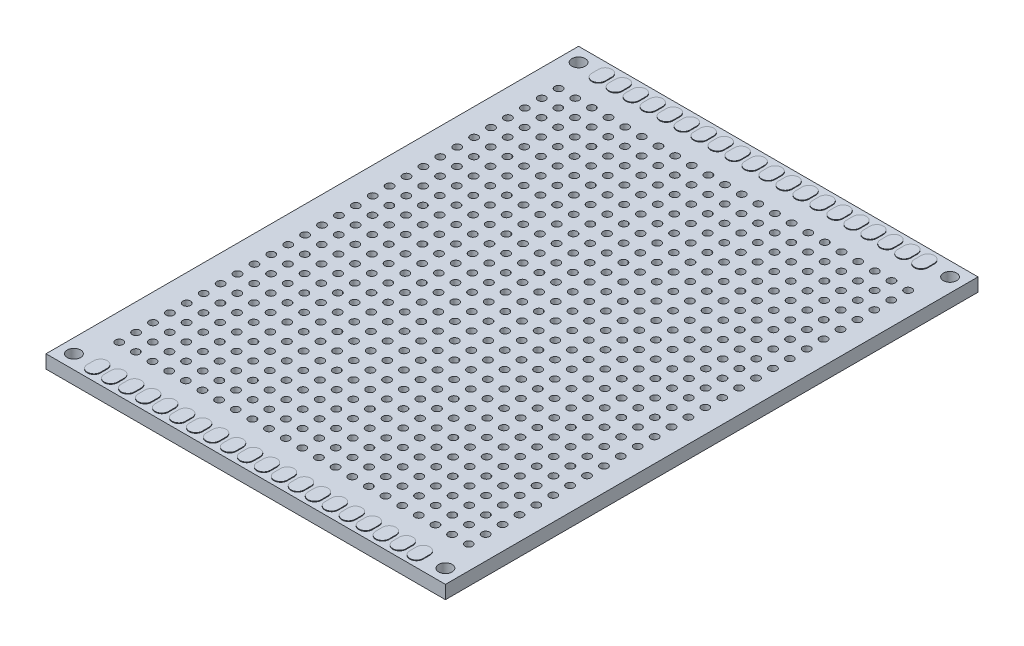
SolidWorks part; units mm, degrees
ref_plane "Front Plane" through (0, 0, 0) normal (0, 0, 1) x (1, 0, 0)
ref_plane "Top Plane" through (0, 0, 0) normal (0, 1, 0) x (1, 0, 0)
ref_plane "Right Plane" through (0, 0, 0) normal (1, 0, 0) x (0, 0, -1)
sketch "Sketch1" plane through (0, 0, 0) normal (0, 1, 0) x (1, 0, 0)
  line L0 (4, 73) -> (6.5, 73) construction
  line L1 (0, 80) -> (60, 80)
  line L2 (0, 80) -> (0, 0)
  line L3 (0, 0) -> (60, 0)
  line L4 (60, 80) -> (60, 0)
  circle A0 centre (2.1, 77.9) radius 1
  circle A1 centre (57.9, 77.9) radius 1
  circle A2 centre (2.1, 2.1) radius 1
  circle A3 centre (57.9, 2.1) radius 1
  circle A4 centre (4, 73) radius 0.575
  circle A5 centre (6.5, 73) radius 0.575
  circle A6 centre (9, 73) radius 0.575
  circle A7 centre (11.5, 73) radius 0.575
  circle A8 centre (14, 73) radius 0.575
  circle A9 centre (16.5, 73) radius 0.575
  circle A10 centre (19, 73) radius 0.575
  circle A11 centre (21.5, 73) radius 0.575
  circle A12 centre (24, 73) radius 0.575
  circle A13 centre (26.5, 73) radius 0.575
  circle A14 centre (29, 73) radius 0.575
  circle A15 centre (31.5, 73) radius 0.575
  circle A16 centre (34, 73) radius 0.575
  circle A17 centre (36.5, 73) radius 0.575
  circle A18 centre (39, 73) radius 0.575
  circle A19 centre (41.5, 73) radius 0.575
  circle A20 centre (44, 73) radius 0.575
  circle A21 centre (46.5, 73) radius 0.575
  circle A22 centre (49, 73) radius 0.575
  circle A23 centre (51.5, 73) radius 0.575
  circle A24 centre (54, 73) radius 0.575
  circle A25 centre (56.5, 73) radius 0.575
  circle A26 centre (6.5, 70.4615) radius 0.575
  circle A27 centre (9, 70.4615) radius 0.575
  circle A28 centre (11.5, 70.4615) radius 0.575
  circle A29 centre (14, 70.4615) radius 0.575
  circle A30 centre (16.5, 70.4615) radius 0.575
  circle A31 centre (19, 70.4615) radius 0.575
  circle A32 centre (21.5, 70.4615) radius 0.575
  circle A33 centre (24, 70.4615) radius 0.575
  circle A34 centre (26.5, 70.4615) radius 0.575
  circle A35 centre (29, 70.4615) radius 0.575
  circle A36 centre (31.5, 70.4615) radius 0.575
  circle A37 centre (34, 70.4615) radius 0.575
  circle A38 centre (36.5, 70.4615) radius 0.575
  circle A39 centre (39, 70.4615) radius 0.575
  circle A40 centre (41.5, 70.4615) radius 0.575
  circle A41 centre (44, 70.4615) radius 0.575
  circle A42 centre (46.5, 70.4615) radius 0.575
  circle A43 centre (49, 70.4615) radius 0.575
  circle A44 centre (51.5, 70.4615) radius 0.575
  circle A45 centre (54, 70.4615) radius 0.575
  circle A46 centre (56.5, 70.4615) radius 0.575
  circle A47 centre (6.5, 67.9231) radius 0.575
  circle A48 centre (9, 67.9231) radius 0.575
  circle A49 centre (11.5, 67.9231) radius 0.575
  circle A50 centre (14, 67.9231) radius 0.575
  circle A51 centre (16.5, 67.9231) radius 0.575
  circle A52 centre (19, 67.9231) radius 0.575
  circle A53 centre (21.5, 67.9231) radius 0.575
  circle A54 centre (24, 67.9231) radius 0.575
  circle A55 centre (26.5, 67.9231) radius 0.575
  circle A56 centre (29, 67.9231) radius 0.575
  circle A57 centre (31.5, 67.9231) radius 0.575
  circle A58 centre (34, 67.9231) radius 0.575
  circle A59 centre (36.5, 67.9231) radius 0.575
  circle A60 centre (39, 67.9231) radius 0.575
  circle A61 centre (41.5, 67.9231) radius 0.575
  circle A62 centre (44, 67.9231) radius 0.575
  circle A63 centre (46.5, 67.9231) radius 0.575
  circle A64 centre (49, 67.9231) radius 0.575
  circle A65 centre (51.5, 67.9231) radius 0.575
  circle A66 centre (54, 67.9231) radius 0.575
  circle A67 centre (56.5, 67.9231) radius 0.575
  circle A68 centre (6.5, 65.3846) radius 0.575
  circle A69 centre (9, 65.3846) radius 0.575
  circle A70 centre (11.5, 65.3846) radius 0.575
  circle A71 centre (14, 65.3846) radius 0.575
  circle A72 centre (16.5, 65.3846) radius 0.575
  circle A73 centre (19, 65.3846) radius 0.575
  circle A74 centre (21.5, 65.3846) radius 0.575
  circle A75 centre (24, 65.3846) radius 0.575
  circle A76 centre (26.5, 65.3846) radius 0.575
  circle A77 centre (29, 65.3846) radius 0.575
  circle A78 centre (31.5, 65.3846) radius 0.575
  circle A79 centre (34, 65.3846) radius 0.575
  circle A80 centre (36.5, 65.3846) radius 0.575
  circle A81 centre (39, 65.3846) radius 0.575
  circle A82 centre (41.5, 65.3846) radius 0.575
  circle A83 centre (44, 65.3846) radius 0.575
  circle A84 centre (46.5, 65.3846) radius 0.575
  circle A85 centre (49, 65.3846) radius 0.575
  circle A86 centre (51.5, 65.3846) radius 0.575
  circle A87 centre (54, 65.3846) radius 0.575
  circle A88 centre (56.5, 65.3846) radius 0.575
  circle A89 centre (6.5, 62.8462) radius 0.575
  circle A90 centre (9, 62.8462) radius 0.575
  circle A91 centre (11.5, 62.8462) radius 0.575
  circle A92 centre (14, 62.8462) radius 0.575
  circle A93 centre (16.5, 62.8462) radius 0.575
  circle A94 centre (19, 62.8462) radius 0.575
  circle A95 centre (21.5, 62.8462) radius 0.575
  circle A96 centre (24, 62.8462) radius 0.575
  circle A97 centre (26.5, 62.8462) radius 0.575
  circle A98 centre (29, 62.8462) radius 0.575
  circle A99 centre (31.5, 62.8462) radius 0.575
  circle A100 centre (34, 62.8462) radius 0.575
  circle A101 centre (36.5, 62.8462) radius 0.575
  circle A102 centre (39, 62.8462) radius 0.575
  circle A103 centre (41.5, 62.8462) radius 0.575
  circle A104 centre (44, 62.8462) radius 0.575
  circle A105 centre (46.5, 62.8462) radius 0.575
  circle A106 centre (49, 62.8462) radius 0.575
  circle A107 centre (51.5, 62.8462) radius 0.575
  circle A108 centre (54, 62.8462) radius 0.575
  circle A109 centre (56.5, 62.8462) radius 0.575
  circle A110 centre (6.5, 60.3077) radius 0.575
  circle A111 centre (9, 60.3077) radius 0.575
  circle A112 centre (11.5, 60.3077) radius 0.575
  circle A113 centre (14, 60.3077) radius 0.575
  circle A114 centre (16.5, 60.3077) radius 0.575
  circle A115 centre (19, 60.3077) radius 0.575
  circle A116 centre (21.5, 60.3077) radius 0.575
  circle A117 centre (24, 60.3077) radius 0.575
  circle A118 centre (26.5, 60.3077) radius 0.575
  circle A119 centre (29, 60.3077) radius 0.575
  circle A120 centre (31.5, 60.3077) radius 0.575
  circle A121 centre (34, 60.3077) radius 0.575
  circle A122 centre (36.5, 60.3077) radius 0.575
  circle A123 centre (39, 60.3077) radius 0.575
  circle A124 centre (41.5, 60.3077) radius 0.575
  circle A125 centre (44, 60.3077) radius 0.575
  circle A126 centre (46.5, 60.3077) radius 0.575
  circle A127 centre (49, 60.3077) radius 0.575
  circle A128 centre (51.5, 60.3077) radius 0.575
  circle A129 centre (54, 60.3077) radius 0.575
  circle A130 centre (56.5, 60.3077) radius 0.575
  circle A131 centre (6.5, 57.7692) radius 0.575
  circle A132 centre (9, 57.7692) radius 0.575
  circle A133 centre (11.5, 57.7692) radius 0.575
  circle A134 centre (14, 57.7692) radius 0.575
  circle A135 centre (16.5, 57.7692) radius 0.575
  circle A136 centre (19, 57.7692) radius 0.575
  circle A137 centre (21.5, 57.7692) radius 0.575
  circle A138 centre (24, 57.7692) radius 0.575
  circle A139 centre (26.5, 57.7692) radius 0.575
  circle A140 centre (29, 57.7692) radius 0.575
  circle A141 centre (31.5, 57.7692) radius 0.575
  circle A142 centre (34, 57.7692) radius 0.575
  circle A143 centre (36.5, 57.7692) radius 0.575
  circle A144 centre (39, 57.7692) radius 0.575
  circle A145 centre (41.5, 57.7692) radius 0.575
  circle A146 centre (44, 57.7692) radius 0.575
  circle A147 centre (46.5, 57.7692) radius 0.575
  circle A148 centre (49, 57.7692) radius 0.575
  circle A149 centre (51.5, 57.7692) radius 0.575
  circle A150 centre (54, 57.7692) radius 0.575
  circle A151 centre (56.5, 57.7692) radius 0.575
  circle A152 centre (6.5, 55.2308) radius 0.575
  circle A153 centre (9, 55.2308) radius 0.575
  circle A154 centre (11.5, 55.2308) radius 0.575
  circle A155 centre (14, 55.2308) radius 0.575
  circle A156 centre (16.5, 55.2308) radius 0.575
  circle A157 centre (19, 55.2308) radius 0.575
  circle A158 centre (21.5, 55.2308) radius 0.575
  circle A159 centre (24, 55.2308) radius 0.575
  circle A160 centre (26.5, 55.2308) radius 0.575
  circle A161 centre (29, 55.2308) radius 0.575
  circle A162 centre (31.5, 55.2308) radius 0.575
  circle A163 centre (34, 55.2308) radius 0.575
  circle A164 centre (36.5, 55.2308) radius 0.575
  circle A165 centre (39, 55.2308) radius 0.575
  circle A166 centre (41.5, 55.2308) radius 0.575
  circle A167 centre (44, 55.2308) radius 0.575
  circle A168 centre (46.5, 55.2308) radius 0.575
  circle A169 centre (49, 55.2308) radius 0.575
  circle A170 centre (51.5, 55.2308) radius 0.575
  circle A171 centre (54, 55.2308) radius 0.575
  circle A172 centre (56.5, 55.2308) radius 0.575
  circle A173 centre (6.5, 52.6923) radius 0.575
  circle A174 centre (9, 52.6923) radius 0.575
  circle A175 centre (11.5, 52.6923) radius 0.575
  circle A176 centre (14, 52.6923) radius 0.575
  circle A177 centre (16.5, 52.6923) radius 0.575
  circle A178 centre (19, 52.6923) radius 0.575
  circle A179 centre (21.5, 52.6923) radius 0.575
  circle A180 centre (24, 52.6923) radius 0.575
  circle A181 centre (26.5, 52.6923) radius 0.575
  circle A182 centre (29, 52.6923) radius 0.575
  circle A183 centre (31.5, 52.6923) radius 0.575
  circle A184 centre (34, 52.6923) radius 0.575
  circle A185 centre (36.5, 52.6923) radius 0.575
  circle A186 centre (39, 52.6923) radius 0.575
  circle A187 centre (41.5, 52.6923) radius 0.575
  circle A188 centre (44, 52.6923) radius 0.575
  circle A189 centre (46.5, 52.6923) radius 0.575
  circle A190 centre (49, 52.6923) radius 0.575
  circle A191 centre (51.5, 52.6923) radius 0.575
  circle A192 centre (54, 52.6923) radius 0.575
  circle A193 centre (56.5, 52.6923) radius 0.575
  circle A194 centre (6.5, 50.1538) radius 0.575
  circle A195 centre (9, 50.1538) radius 0.575
  circle A196 centre (11.5, 50.1538) radius 0.575
  circle A197 centre (14, 50.1538) radius 0.575
  circle A198 centre (16.5, 50.1538) radius 0.575
  circle A199 centre (19, 50.1538) radius 0.575
  circle A200 centre (21.5, 50.1538) radius 0.575
  circle A201 centre (24, 50.1538) radius 0.575
  circle A202 centre (26.5, 50.1538) radius 0.575
  circle A203 centre (29, 50.1538) radius 0.575
  circle A204 centre (31.5, 50.1538) radius 0.575
  circle A205 centre (34, 50.1538) radius 0.575
  circle A206 centre (36.5, 50.1538) radius 0.575
  circle A207 centre (39, 50.1538) radius 0.575
  circle A208 centre (41.5, 50.1538) radius 0.575
  circle A209 centre (44, 50.1538) radius 0.575
  circle A210 centre (46.5, 50.1538) radius 0.575
  circle A211 centre (49, 50.1538) radius 0.575
  circle A212 centre (51.5, 50.1538) radius 0.575
  circle A213 centre (54, 50.1538) radius 0.575
  circle A214 centre (56.5, 50.1538) radius 0.575
  circle A215 centre (6.5, 47.6154) radius 0.575
  circle A216 centre (9, 47.6154) radius 0.575
  circle A217 centre (11.5, 47.6154) radius 0.575
  circle A218 centre (14, 47.6154) radius 0.575
  circle A219 centre (16.5, 47.6154) radius 0.575
  circle A220 centre (19, 47.6154) radius 0.575
  circle A221 centre (21.5, 47.6154) radius 0.575
  circle A222 centre (24, 47.6154) radius 0.575
  circle A223 centre (26.5, 47.6154) radius 0.575
  circle A224 centre (29, 47.6154) radius 0.575
  circle A225 centre (31.5, 47.6154) radius 0.575
  circle A226 centre (34, 47.6154) radius 0.575
  circle A227 centre (36.5, 47.6154) radius 0.575
  circle A228 centre (39, 47.6154) radius 0.575
  circle A229 centre (41.5, 47.6154) radius 0.575
  circle A230 centre (44, 47.6154) radius 0.575
  circle A231 centre (46.5, 47.6154) radius 0.575
  circle A232 centre (49, 47.6154) radius 0.575
  circle A233 centre (51.5, 47.6154) radius 0.575
  circle A234 centre (54, 47.6154) radius 0.575
  circle A235 centre (56.5, 47.6154) radius 0.575
  circle A236 centre (6.5, 45.0769) radius 0.575
  circle A237 centre (9, 45.0769) radius 0.575
  circle A238 centre (11.5, 45.0769) radius 0.575
  circle A239 centre (14, 45.0769) radius 0.575
  circle A240 centre (16.5, 45.0769) radius 0.575
  circle A241 centre (19, 45.0769) radius 0.575
  circle A242 centre (21.5, 45.0769) radius 0.575
  circle A243 centre (24, 45.0769) radius 0.575
  circle A244 centre (26.5, 45.0769) radius 0.575
  circle A245 centre (29, 45.0769) radius 0.575
  circle A246 centre (31.5, 45.0769) radius 0.575
  circle A247 centre (34, 45.0769) radius 0.575
  circle A248 centre (36.5, 45.0769) radius 0.575
  circle A249 centre (39, 45.0769) radius 0.575
  circle A250 centre (41.5, 45.0769) radius 0.575
  circle A251 centre (44, 45.0769) radius 0.575
  circle A252 centre (46.5, 45.0769) radius 0.575
  circle A253 centre (49, 45.0769) radius 0.575
  circle A254 centre (51.5, 45.0769) radius 0.575
  circle A255 centre (54, 45.0769) radius 0.575
  circle A256 centre (56.5, 45.0769) radius 0.575
  circle A257 centre (6.5, 42.5385) radius 0.575
  circle A258 centre (9, 42.5385) radius 0.575
  circle A259 centre (11.5, 42.5385) radius 0.575
  circle A260 centre (14, 42.5385) radius 0.575
  circle A261 centre (16.5, 42.5385) radius 0.575
  circle A262 centre (19, 42.5385) radius 0.575
  circle A263 centre (21.5, 42.5385) radius 0.575
  circle A264 centre (24, 42.5385) radius 0.575
  circle A265 centre (26.5, 42.5385) radius 0.575
  circle A266 centre (29, 42.5385) radius 0.575
  circle A267 centre (31.5, 42.5385) radius 0.575
  circle A268 centre (34, 42.5385) radius 0.575
  circle A269 centre (36.5, 42.5385) radius 0.575
  circle A270 centre (39, 42.5385) radius 0.575
  circle A271 centre (41.5, 42.5385) radius 0.575
  circle A272 centre (44, 42.5385) radius 0.575
  circle A273 centre (46.5, 42.5385) radius 0.575
  circle A274 centre (49, 42.5385) radius 0.575
  circle A275 centre (51.5, 42.5385) radius 0.575
  circle A276 centre (54, 42.5385) radius 0.575
  circle A277 centre (56.5, 42.5385) radius 0.575
  circle A278 centre (6.5, 40) radius 0.575
  circle A279 centre (9, 40) radius 0.575
  circle A280 centre (11.5, 40) radius 0.575
  circle A281 centre (14, 40) radius 0.575
  circle A282 centre (16.5, 40) radius 0.575
  circle A283 centre (19, 40) radius 0.575
  circle A284 centre (21.5, 40) radius 0.575
  circle A285 centre (24, 40) radius 0.575
  circle A286 centre (26.5, 40) radius 0.575
  circle A287 centre (29, 40) radius 0.575
  circle A288 centre (31.5, 40) radius 0.575
  circle A289 centre (34, 40) radius 0.575
  circle A290 centre (36.5, 40) radius 0.575
  circle A291 centre (39, 40) radius 0.575
  circle A292 centre (41.5, 40) radius 0.575
  circle A293 centre (44, 40) radius 0.575
  circle A294 centre (46.5, 40) radius 0.575
  circle A295 centre (49, 40) radius 0.575
  circle A296 centre (51.5, 40) radius 0.575
  circle A297 centre (54, 40) radius 0.575
  circle A298 centre (56.5, 40) radius 0.575
  circle A299 centre (6.5, 37.4615) radius 0.575
  circle A300 centre (9, 37.4615) radius 0.575
  circle A301 centre (11.5, 37.4615) radius 0.575
  circle A302 centre (14, 37.4615) radius 0.575
  circle A303 centre (16.5, 37.4615) radius 0.575
  circle A304 centre (19, 37.4615) radius 0.575
  circle A305 centre (21.5, 37.4615) radius 0.575
  circle A306 centre (24, 37.4615) radius 0.575
  circle A307 centre (26.5, 37.4615) radius 0.575
  circle A308 centre (29, 37.4615) radius 0.575
  circle A309 centre (31.5, 37.4615) radius 0.575
  circle A310 centre (34, 37.4615) radius 0.575
  circle A311 centre (36.5, 37.4615) radius 0.575
  circle A312 centre (39, 37.4615) radius 0.575
  circle A313 centre (41.5, 37.4615) radius 0.575
  circle A314 centre (44, 37.4615) radius 0.575
  circle A315 centre (46.5, 37.4615) radius 0.575
  circle A316 centre (49, 37.4615) radius 0.575
  circle A317 centre (51.5, 37.4615) radius 0.575
  circle A318 centre (54, 37.4615) radius 0.575
  circle A319 centre (56.5, 37.4615) radius 0.575
  circle A320 centre (6.5, 34.9231) radius 0.575
  circle A321 centre (9, 34.9231) radius 0.575
  circle A322 centre (11.5, 34.9231) radius 0.575
  circle A323 centre (14, 34.9231) radius 0.575
  circle A324 centre (16.5, 34.9231) radius 0.575
  circle A325 centre (19, 34.9231) radius 0.575
  circle A326 centre (21.5, 34.9231) radius 0.575
  circle A327 centre (24, 34.9231) radius 0.575
  circle A328 centre (26.5, 34.9231) radius 0.575
  circle A329 centre (29, 34.9231) radius 0.575
  circle A330 centre (31.5, 34.9231) radius 0.575
  circle A331 centre (34, 34.9231) radius 0.575
  circle A332 centre (36.5, 34.9231) radius 0.575
  circle A333 centre (39, 34.9231) radius 0.575
  circle A334 centre (41.5, 34.9231) radius 0.575
  circle A335 centre (44, 34.9231) radius 0.575
  circle A336 centre (46.5, 34.9231) radius 0.575
  circle A337 centre (49, 34.9231) radius 0.575
  circle A338 centre (51.5, 34.9231) radius 0.575
  circle A339 centre (54, 34.9231) radius 0.575
  circle A340 centre (56.5, 34.9231) radius 0.575
  circle A341 centre (6.5, 32.3846) radius 0.575
  circle A342 centre (9, 32.3846) radius 0.575
  circle A343 centre (11.5, 32.3846) radius 0.575
  circle A344 centre (14, 32.3846) radius 0.575
  circle A345 centre (16.5, 32.3846) radius 0.575
  circle A346 centre (19, 32.3846) radius 0.575
  circle A347 centre (21.5, 32.3846) radius 0.575
  circle A348 centre (24, 32.3846) radius 0.575
  circle A349 centre (26.5, 32.3846) radius 0.575
  circle A350 centre (29, 32.3846) radius 0.575
  circle A351 centre (31.5, 32.3846) radius 0.575
  circle A352 centre (34, 32.3846) radius 0.575
  circle A353 centre (36.5, 32.3846) radius 0.575
  circle A354 centre (39, 32.3846) radius 0.575
  circle A355 centre (41.5, 32.3846) radius 0.575
  circle A356 centre (44, 32.3846) radius 0.575
  circle A357 centre (46.5, 32.3846) radius 0.575
  circle A358 centre (49, 32.3846) radius 0.575
  circle A359 centre (51.5, 32.3846) radius 0.575
  circle A360 centre (54, 32.3846) radius 0.575
  circle A361 centre (56.5, 32.3846) radius 0.575
  circle A362 centre (6.5, 29.8462) radius 0.575
  circle A363 centre (9, 29.8462) radius 0.575
  circle A364 centre (11.5, 29.8462) radius 0.575
  circle A365 centre (14, 29.8462) radius 0.575
  circle A366 centre (16.5, 29.8462) radius 0.575
  circle A367 centre (19, 29.8462) radius 0.575
  circle A368 centre (21.5, 29.8462) radius 0.575
  circle A369 centre (24, 29.8462) radius 0.575
  circle A370 centre (26.5, 29.8462) radius 0.575
  circle A371 centre (29, 29.8462) radius 0.575
  circle A372 centre (31.5, 29.8462) radius 0.575
  circle A373 centre (34, 29.8462) radius 0.575
  circle A374 centre (36.5, 29.8462) radius 0.575
  circle A375 centre (39, 29.8462) radius 0.575
  circle A376 centre (41.5, 29.8462) radius 0.575
  circle A377 centre (44, 29.8462) radius 0.575
  circle A378 centre (46.5, 29.8462) radius 0.575
  circle A379 centre (49, 29.8462) radius 0.575
  circle A380 centre (51.5, 29.8462) radius 0.575
  circle A381 centre (54, 29.8462) radius 0.575
  circle A382 centre (56.5, 29.8462) radius 0.575
  circle A383 centre (6.5, 27.3077) radius 0.575
  circle A384 centre (9, 27.3077) radius 0.575
  circle A385 centre (11.5, 27.3077) radius 0.575
  circle A386 centre (14, 27.3077) radius 0.575
  circle A387 centre (16.5, 27.3077) radius 0.575
  circle A388 centre (19, 27.3077) radius 0.575
  circle A389 centre (21.5, 27.3077) radius 0.575
  circle A390 centre (24, 27.3077) radius 0.575
  circle A391 centre (26.5, 27.3077) radius 0.575
  circle A392 centre (29, 27.3077) radius 0.575
  circle A393 centre (31.5, 27.3077) radius 0.575
  circle A394 centre (34, 27.3077) radius 0.575
  circle A395 centre (36.5, 27.3077) radius 0.575
  circle A396 centre (39, 27.3077) radius 0.575
  circle A397 centre (41.5, 27.3077) radius 0.575
  circle A398 centre (44, 27.3077) radius 0.575
  circle A399 centre (46.5, 27.3077) radius 0.575
  circle A400 centre (49, 27.3077) radius 0.575
  circle A401 centre (51.5, 27.3077) radius 0.575
  circle A402 centre (54, 27.3077) radius 0.575
  circle A403 centre (56.5, 27.3077) radius 0.575
  circle A404 centre (6.5, 24.7692) radius 0.575
  circle A405 centre (9, 24.7692) radius 0.575
  circle A406 centre (11.5, 24.7692) radius 0.575
  circle A407 centre (14, 24.7692) radius 0.575
  circle A408 centre (16.5, 24.7692) radius 0.575
  circle A409 centre (19, 24.7692) radius 0.575
  circle A410 centre (21.5, 24.7692) radius 0.575
  circle A411 centre (24, 24.7692) radius 0.575
  circle A412 centre (26.5, 24.7692) radius 0.575
  circle A413 centre (29, 24.7692) radius 0.575
  circle A414 centre (31.5, 24.7692) radius 0.575
  circle A415 centre (34, 24.7692) radius 0.575
  circle A416 centre (36.5, 24.7692) radius 0.575
  circle A417 centre (39, 24.7692) radius 0.575
  circle A418 centre (41.5, 24.7692) radius 0.575
  circle A419 centre (44, 24.7692) radius 0.575
  circle A420 centre (46.5, 24.7692) radius 0.575
  circle A421 centre (49, 24.7692) radius 0.575
  circle A422 centre (51.5, 24.7692) radius 0.575
  circle A423 centre (54, 24.7692) radius 0.575
  circle A424 centre (56.5, 24.7692) radius 0.575
  circle A425 centre (6.5, 22.2308) radius 0.575
  circle A426 centre (9, 22.2308) radius 0.575
  circle A427 centre (11.5, 22.2308) radius 0.575
  circle A428 centre (14, 22.2308) radius 0.575
  circle A429 centre (16.5, 22.2308) radius 0.575
  circle A430 centre (19, 22.2308) radius 0.575
  circle A431 centre (21.5, 22.2308) radius 0.575
  circle A432 centre (24, 22.2308) radius 0.575
  circle A433 centre (26.5, 22.2308) radius 0.575
  circle A434 centre (29, 22.2308) radius 0.575
  circle A435 centre (31.5, 22.2308) radius 0.575
  circle A436 centre (34, 22.2308) radius 0.575
  circle A437 centre (36.5, 22.2308) radius 0.575
  circle A438 centre (39, 22.2308) radius 0.575
  circle A439 centre (41.5, 22.2308) radius 0.575
  circle A440 centre (44, 22.2308) radius 0.575
  circle A441 centre (46.5, 22.2308) radius 0.575
  circle A442 centre (49, 22.2308) radius 0.575
  circle A443 centre (51.5, 22.2308) radius 0.575
  circle A444 centre (54, 22.2308) radius 0.575
  circle A445 centre (56.5, 22.2308) radius 0.575
  circle A446 centre (6.5, 19.6923) radius 0.575
  circle A447 centre (9, 19.6923) radius 0.575
  circle A448 centre (11.5, 19.6923) radius 0.575
  circle A449 centre (14, 19.6923) radius 0.575
  circle A450 centre (16.5, 19.6923) radius 0.575
  circle A451 centre (19, 19.6923) radius 0.575
  circle A452 centre (21.5, 19.6923) radius 0.575
  circle A453 centre (24, 19.6923) radius 0.575
  circle A454 centre (26.5, 19.6923) radius 0.575
  circle A455 centre (29, 19.6923) radius 0.575
  circle A456 centre (31.5, 19.6923) radius 0.575
  circle A457 centre (34, 19.6923) radius 0.575
  circle A458 centre (36.5, 19.6923) radius 0.575
  circle A459 centre (39, 19.6923) radius 0.575
  circle A460 centre (41.5, 19.6923) radius 0.575
  circle A461 centre (44, 19.6923) radius 0.575
  circle A462 centre (46.5, 19.6923) radius 0.575
  circle A463 centre (49, 19.6923) radius 0.575
  circle A464 centre (51.5, 19.6923) radius 0.575
  circle A465 centre (54, 19.6923) radius 0.575
  circle A466 centre (56.5, 19.6923) radius 0.575
  circle A467 centre (6.5, 17.1538) radius 0.575
  circle A468 centre (9, 17.1538) radius 0.575
  circle A469 centre (11.5, 17.1538) radius 0.575
  circle A470 centre (14, 17.1538) radius 0.575
  circle A471 centre (16.5, 17.1538) radius 0.575
  circle A472 centre (19, 17.1538) radius 0.575
  circle A473 centre (21.5, 17.1538) radius 0.575
  circle A474 centre (24, 17.1538) radius 0.575
  circle A475 centre (26.5, 17.1538) radius 0.575
  circle A476 centre (29, 17.1538) radius 0.575
  circle A477 centre (31.5, 17.1538) radius 0.575
  circle A478 centre (34, 17.1538) radius 0.575
  circle A479 centre (36.5, 17.1538) radius 0.575
  circle A480 centre (39, 17.1538) radius 0.575
  circle A481 centre (41.5, 17.1538) radius 0.575
  circle A482 centre (44, 17.1538) radius 0.575
  circle A483 centre (46.5, 17.1538) radius 0.575
  circle A484 centre (49, 17.1538) radius 0.575
  circle A485 centre (51.5, 17.1538) radius 0.575
  circle A486 centre (54, 17.1538) radius 0.575
  circle A487 centre (56.5, 17.1538) radius 0.575
  circle A488 centre (6.5, 14.6154) radius 0.575
  circle A489 centre (9, 14.6154) radius 0.575
  circle A490 centre (11.5, 14.6154) radius 0.575
  circle A491 centre (14, 14.6154) radius 0.575
  circle A492 centre (16.5, 14.6154) radius 0.575
  circle A493 centre (19, 14.6154) radius 0.575
  circle A494 centre (21.5, 14.6154) radius 0.575
  circle A495 centre (24, 14.6154) radius 0.575
  circle A496 centre (26.5, 14.6154) radius 0.575
  circle A497 centre (29, 14.6154) radius 0.575
  circle A498 centre (31.5, 14.6154) radius 0.575
  circle A499 centre (34, 14.6154) radius 0.575
  circle A500 centre (36.5, 14.6154) radius 0.575
  circle A501 centre (39, 14.6154) radius 0.575
  circle A502 centre (41.5, 14.6154) radius 0.575
  circle A503 centre (44, 14.6154) radius 0.575
  circle A504 centre (46.5, 14.6154) radius 0.575
  circle A505 centre (49, 14.6154) radius 0.575
  circle A506 centre (51.5, 14.6154) radius 0.575
  circle A507 centre (54, 14.6154) radius 0.575
  circle A508 centre (56.5, 14.6154) radius 0.575
  circle A509 centre (6.5, 12.0769) radius 0.575
  circle A510 centre (9, 12.0769) radius 0.575
  circle A511 centre (11.5, 12.0769) radius 0.575
  circle A512 centre (14, 12.0769) radius 0.575
  circle A513 centre (16.5, 12.0769) radius 0.575
  circle A514 centre (19, 12.0769) radius 0.575
  circle A515 centre (21.5, 12.0769) radius 0.575
  circle A516 centre (24, 12.0769) radius 0.575
  circle A517 centre (26.5, 12.0769) radius 0.575
  circle A518 centre (29, 12.0769) radius 0.575
  circle A519 centre (31.5, 12.0769) radius 0.575
  circle A520 centre (34, 12.0769) radius 0.575
  circle A521 centre (36.5, 12.0769) radius 0.575
  circle A522 centre (39, 12.0769) radius 0.575
  circle A523 centre (41.5, 12.0769) radius 0.575
  circle A524 centre (44, 12.0769) radius 0.575
  circle A525 centre (46.5, 12.0769) radius 0.575
  circle A526 centre (49, 12.0769) radius 0.575
  circle A527 centre (51.5, 12.0769) radius 0.575
  circle A528 centre (54, 12.0769) radius 0.575
  circle A529 centre (56.5, 12.0769) radius 0.575
  circle A530 centre (6.5, 9.5385) radius 0.575
  circle A531 centre (9, 9.5385) radius 0.575
  circle A532 centre (11.5, 9.5385) radius 0.575
  circle A533 centre (14, 9.5385) radius 0.575
  circle A534 centre (16.5, 9.5385) radius 0.575
  circle A535 centre (19, 9.5385) radius 0.575
  circle A536 centre (21.5, 9.5385) radius 0.575
  circle A537 centre (24, 9.5385) radius 0.575
  circle A538 centre (26.5, 9.5385) radius 0.575
  circle A539 centre (29, 9.5385) radius 0.575
  circle A540 centre (31.5, 9.5385) radius 0.575
  circle A541 centre (34, 9.5385) radius 0.575
  circle A542 centre (36.5, 9.5385) radius 0.575
  circle A543 centre (39, 9.5385) radius 0.575
  circle A544 centre (41.5, 9.5385) radius 0.575
  circle A545 centre (44, 9.5385) radius 0.575
  circle A546 centre (46.5, 9.5385) radius 0.575
  circle A547 centre (49, 9.5385) radius 0.575
  circle A548 centre (51.5, 9.5385) radius 0.575
  circle A549 centre (54, 9.5385) radius 0.575
  circle A550 centre (56.5, 9.5385) radius 0.575
  circle A551 centre (6.5, 7) radius 0.575
  circle A552 centre (9, 7) radius 0.575
  circle A553 centre (11.5, 7) radius 0.575
  circle A554 centre (14, 7) radius 0.575
  circle A555 centre (16.5, 7) radius 0.575
  circle A556 centre (19, 7) radius 0.575
  circle A557 centre (21.5, 7) radius 0.575
  circle A558 centre (24, 7) radius 0.575
  circle A559 centre (26.5, 7) radius 0.575
  circle A560 centre (29, 7) radius 0.575
  circle A561 centre (31.5, 7) radius 0.575
  circle A562 centre (34, 7) radius 0.575
  circle A563 centre (36.5, 7) radius 0.575
  circle A564 centre (39, 7) radius 0.575
  circle A565 centre (41.5, 7) radius 0.575
  circle A566 centre (44, 7) radius 0.575
  circle A567 centre (46.5, 7) radius 0.575
  circle A568 centre (49, 7) radius 0.575
  circle A569 centre (51.5, 7) radius 0.575
  circle A570 centre (54, 7) radius 0.575
  circle A571 centre (56.5, 7) radius 0.575
  circle A572 centre (4, 70.4615) radius 0.575
  circle A573 centre (4, 67.9231) radius 0.575
  circle A574 centre (4, 65.3846) radius 0.575
  circle A575 centre (4, 62.8462) radius 0.575
  circle A576 centre (4, 60.3077) radius 0.575
  circle A577 centre (4, 57.7692) radius 0.575
  circle A578 centre (4, 55.2308) radius 0.575
  circle A579 centre (4, 52.6923) radius 0.575
  circle A580 centre (4, 50.1538) radius 0.575
  circle A581 centre (4, 47.6154) radius 0.575
  circle A582 centre (4, 45.0769) radius 0.575
  circle A583 centre (4, 42.5385) radius 0.575
  circle A584 centre (4, 40) radius 0.575
  circle A585 centre (4, 37.4615) radius 0.575
  circle A586 centre (4, 34.9231) radius 0.575
  circle A587 centre (4, 32.3846) radius 0.575
  circle A588 centre (4, 29.8462) radius 0.575
  circle A589 centre (4, 27.3077) radius 0.575
  circle A590 centre (4, 24.7692) radius 0.575
  circle A591 centre (4, 22.2308) radius 0.575
  circle A592 centre (4, 19.6923) radius 0.575
  circle A593 centre (4, 17.1538) radius 0.575
  circle A594 centre (4, 14.6154) radius 0.575
  circle A595 centre (4, 12.0769) radius 0.575
  circle A596 centre (4, 9.5385) radius 0.575
  circle A597 centre (4, 7) radius 0.575
  dimension "D3" = 2
  dimension "D12" = 1.15
  dimension "D1" = 60
  dimension "D2" = 80
  dimension "D4" = 2.1
  dimension "D5" = 2.1
  dimension "D6" = 2.1
  dimension "D7" = 2.1
  dimension "D8" = 2.1
  dimension "D9" = 2.1
  dimension "D10" = 2.1
  dimension "D11" = 2.1
  dimension "D15" = 2.5
  dimension "D16" = 7
  dimension "D17" = 4
  dimension "D18" = 66
  dimension "D13" = 22
  dimension "D14" = 27
extrude "Boss-Extrude1" add sketch "Sketch1" along normal blind 2
sketch "Sketch2" plane through (0, 2, 0) normal (0, 1, 0) x (1, 0, 0)
  line L0 (5.6, 78.4) -> (5.6, 77.4) construction
  line L1 (6.6, 78.4) -> (6.6, 77.4)
  line L2 (4.6, 78.4) -> (4.6, 77.4)
  line L3 (4.3933, 79.4) -> (8.7363, 79.4) construction
  line L4 (4.162, 76.4) -> (8.5436, 76.4) construction
  line L5 (2.1, 77.9) -> (8.081, 77.9) construction
  line L6 (8.15, 78.4) -> (8.15, 77.4) construction
  line L7 (9.15, 78.4) -> (9.15, 77.4)
  line L8 (7.15, 78.4) -> (7.15, 77.4)
  line L9 (10.7, 78.4) -> (10.7, 77.4) construction
  line L10 (11.7, 78.4) -> (11.7, 77.4)
  line L11 (9.7, 78.4) -> (9.7, 77.4)
  line L12 (13.25, 78.4) -> (13.25, 77.4) construction
  line L13 (14.25, 78.4) -> (14.25, 77.4)
  line L14 (12.25, 78.4) -> (12.25, 77.4)
  line L15 (15.8, 78.4) -> (15.8, 77.4) construction
  line L16 (16.8, 78.4) -> (16.8, 77.4)
  line L17 (14.8, 78.4) -> (14.8, 77.4)
  line L18 (18.35, 78.4) -> (18.35, 77.4) construction
  line L19 (19.35, 78.4) -> (19.35, 77.4)
  line L20 (17.35, 78.4) -> (17.35, 77.4)
  line L21 (20.9, 78.4) -> (20.9, 77.4) construction
  line L22 (21.9, 78.4) -> (21.9, 77.4)
  line L23 (19.9, 78.4) -> (19.9, 77.4)
  line L24 (23.45, 78.4) -> (23.45, 77.4) construction
  line L25 (24.45, 78.4) -> (24.45, 77.4)
  line L26 (22.45, 78.4) -> (22.45, 77.4)
  line L27 (26, 78.4) -> (26, 77.4) construction
  line L28 (27, 78.4) -> (27, 77.4)
  line L29 (25, 78.4) -> (25, 77.4)
  line L30 (28.55, 78.4) -> (28.55, 77.4) construction
  line L31 (29.55, 78.4) -> (29.55, 77.4)
  line L32 (27.55, 78.4) -> (27.55, 77.4)
  line L33 (31.1, 78.4) -> (31.1, 77.4) construction
  line L34 (32.1, 78.4) -> (32.1, 77.4)
  line L35 (30.1, 78.4) -> (30.1, 77.4)
  line L36 (33.65, 78.4) -> (33.65, 77.4) construction
  line L37 (34.65, 78.4) -> (34.65, 77.4)
  line L38 (32.65, 78.4) -> (32.65, 77.4)
  line L39 (36.2, 78.4) -> (36.2, 77.4) construction
  line L40 (37.2, 78.4) -> (37.2, 77.4)
  line L41 (35.2, 78.4) -> (35.2, 77.4)
  line L42 (38.75, 78.4) -> (38.75, 77.4) construction
  line L43 (39.75, 78.4) -> (39.75, 77.4)
  line L44 (37.75, 78.4) -> (37.75, 77.4)
  line L45 (41.3, 78.4) -> (41.3, 77.4) construction
  line L46 (42.3, 78.4) -> (42.3, 77.4)
  line L47 (40.3, 78.4) -> (40.3, 77.4)
  line L48 (43.85, 78.4) -> (43.85, 77.4) construction
  line L49 (44.85, 78.4) -> (44.85, 77.4)
  line L50 (42.85, 78.4) -> (42.85, 77.4)
  line L51 (46.4, 78.4) -> (46.4, 77.4) construction
  line L52 (47.4, 78.4) -> (47.4, 77.4)
  line L53 (45.4, 78.4) -> (45.4, 77.4)
  line L54 (48.95, 78.4) -> (48.95, 77.4) construction
  line L55 (49.95, 78.4) -> (49.95, 77.4)
  line L56 (47.95, 78.4) -> (47.95, 77.4)
  line L57 (51.5, 78.4) -> (51.5, 77.4) construction
  line L58 (52.5, 78.4) -> (52.5, 77.4)
  line L59 (50.5, 78.4) -> (50.5, 77.4)
  line L60 (54.05, 78.4) -> (54.05, 77.4) construction
  line L61 (55.05, 78.4) -> (55.05, 77.4)
  line L62 (53.05, 78.4) -> (53.05, 77.4)
  line L63 (5.6, 78.4) -> (8.15, 78.4) construction
  line L64 (0, 40) -> (76.5553, 40) construction
  line L65 (0, 80) -> (0, 0) construction
  line L66 (5.6, 1.6) -> (5.6, 2.6) construction
  line L67 (6.6, 1.6) -> (6.6, 2.6)
  line L68 (4.6, 1.6) -> (4.6, 2.6)
  line L69 (8.15, 1.6) -> (8.15, 2.6) construction
  line L70 (9.15, 1.6) -> (9.15, 2.6)
  line L71 (7.15, 1.6) -> (7.15, 2.6)
  line L72 (10.7, 1.6) -> (10.7, 2.6) construction
  line L73 (11.7, 1.6) -> (11.7, 2.6)
  line L74 (9.7, 1.6) -> (9.7, 2.6)
  line L75 (13.25, 1.6) -> (13.25, 2.6) construction
  line L76 (14.25, 1.6) -> (14.25, 2.6)
  line L77 (12.25, 1.6) -> (12.25, 2.6)
  line L78 (15.8, 1.6) -> (15.8, 2.6) construction
  line L79 (16.8, 1.6) -> (16.8, 2.6)
  line L80 (14.8, 1.6) -> (14.8, 2.6)
  line L81 (18.35, 1.6) -> (18.35, 2.6) construction
  line L82 (19.35, 1.6) -> (19.35, 2.6)
  line L83 (17.35, 1.6) -> (17.35, 2.6)
  line L84 (20.9, 1.6) -> (20.9, 2.6) construction
  line L85 (21.9, 1.6) -> (21.9, 2.6)
  line L86 (19.9, 1.6) -> (19.9, 2.6)
  line L87 (23.45, 1.6) -> (23.45, 2.6) construction
  line L88 (24.45, 1.6) -> (24.45, 2.6)
  line L89 (22.45, 1.6) -> (22.45, 2.6)
  line L90 (26, 1.6) -> (26, 2.6) construction
  line L91 (27, 1.6) -> (27, 2.6)
  line L92 (25, 1.6) -> (25, 2.6)
  line L93 (28.55, 1.6) -> (28.55, 2.6) construction
  line L94 (29.55, 1.6) -> (29.55, 2.6)
  line L95 (27.55, 1.6) -> (27.55, 2.6)
  line L96 (31.1, 1.6) -> (31.1, 2.6) construction
  line L97 (32.1, 1.6) -> (32.1, 2.6)
  line L98 (30.1, 1.6) -> (30.1, 2.6)
  line L99 (33.65, 1.6) -> (33.65, 2.6) construction
  line L100 (34.65, 1.6) -> (34.65, 2.6)
  line L101 (32.65, 1.6) -> (32.65, 2.6)
  line L102 (36.2, 1.6) -> (36.2, 2.6) construction
  line L103 (37.2, 1.6) -> (37.2, 2.6)
  line L104 (35.2, 1.6) -> (35.2, 2.6)
  line L105 (38.75, 1.6) -> (38.75, 2.6) construction
  line L106 (39.75, 1.6) -> (39.75, 2.6)
  line L107 (37.75, 1.6) -> (37.75, 2.6)
  line L108 (41.3, 1.6) -> (41.3, 2.6) construction
  line L109 (42.3, 1.6) -> (42.3, 2.6)
  line L110 (40.3, 1.6) -> (40.3, 2.6)
  line L111 (43.85, 1.6) -> (43.85, 2.6) construction
  line L112 (44.85, 1.6) -> (44.85, 2.6)
  line L113 (42.85, 1.6) -> (42.85, 2.6)
  line L114 (46.4, 1.6) -> (46.4, 2.6) construction
  line L115 (47.4, 1.6) -> (47.4, 2.6)
  line L116 (45.4, 1.6) -> (45.4, 2.6)
  line L117 (48.95, 1.6) -> (48.95, 2.6) construction
  line L118 (49.95, 1.6) -> (49.95, 2.6)
  line L119 (47.95, 1.6) -> (47.95, 2.6)
  line L120 (51.5, 1.6) -> (51.5, 2.6) construction
  line L121 (52.5, 1.6) -> (52.5, 2.6)
  line L122 (50.5, 1.6) -> (50.5, 2.6)
  line L123 (54.05, 1.6) -> (54.05, 2.6) construction
  line L124 (55.05, 1.6) -> (55.05, 2.6)
  line L125 (53.05, 1.6) -> (53.05, 2.6)
  arc A0 (6.6, 78.4) -> (4.6, 78.4) centre (5.6, 78.4) ccw
  arc A1 (4.6, 77.4) -> (6.6, 77.4) centre (5.6, 77.4) ccw
  arc A2 (9.15, 78.4) -> (7.15, 78.4) centre (8.15, 78.4) ccw
  arc A3 (7.15, 77.4) -> (9.15, 77.4) centre (8.15, 77.4) ccw
  arc A4 (11.7, 78.4) -> (9.7, 78.4) centre (10.7, 78.4) ccw
  arc A5 (9.7, 77.4) -> (11.7, 77.4) centre (10.7, 77.4) ccw
  arc A6 (14.25, 78.4) -> (12.25, 78.4) centre (13.25, 78.4) ccw
  arc A7 (12.25, 77.4) -> (14.25, 77.4) centre (13.25, 77.4) ccw
  arc A8 (16.8, 78.4) -> (14.8, 78.4) centre (15.8, 78.4) ccw
  arc A9 (14.8, 77.4) -> (16.8, 77.4) centre (15.8, 77.4) ccw
  arc A10 (19.35, 78.4) -> (17.35, 78.4) centre (18.35, 78.4) ccw
  arc A11 (17.35, 77.4) -> (19.35, 77.4) centre (18.35, 77.4) ccw
  arc A12 (21.9, 78.4) -> (19.9, 78.4) centre (20.9, 78.4) ccw
  arc A13 (19.9, 77.4) -> (21.9, 77.4) centre (20.9, 77.4) ccw
  arc A14 (24.45, 78.4) -> (22.45, 78.4) centre (23.45, 78.4) ccw
  arc A15 (22.45, 77.4) -> (24.45, 77.4) centre (23.45, 77.4) ccw
  arc A16 (27, 78.4) -> (25, 78.4) centre (26, 78.4) ccw
  arc A17 (25, 77.4) -> (27, 77.4) centre (26, 77.4) ccw
  arc A18 (29.55, 78.4) -> (27.55, 78.4) centre (28.55, 78.4) ccw
  arc A19 (27.55, 77.4) -> (29.55, 77.4) centre (28.55, 77.4) ccw
  arc A20 (32.1, 78.4) -> (30.1, 78.4) centre (31.1, 78.4) ccw
  arc A21 (30.1, 77.4) -> (32.1, 77.4) centre (31.1, 77.4) ccw
  arc A22 (34.65, 78.4) -> (32.65, 78.4) centre (33.65, 78.4) ccw
  arc A23 (32.65, 77.4) -> (34.65, 77.4) centre (33.65, 77.4) ccw
  arc A24 (37.2, 78.4) -> (35.2, 78.4) centre (36.2, 78.4) ccw
  arc A25 (35.2, 77.4) -> (37.2, 77.4) centre (36.2, 77.4) ccw
  arc A26 (39.75, 78.4) -> (37.75, 78.4) centre (38.75, 78.4) ccw
  arc A27 (37.75, 77.4) -> (39.75, 77.4) centre (38.75, 77.4) ccw
  arc A28 (42.3, 78.4) -> (40.3, 78.4) centre (41.3, 78.4) ccw
  arc A29 (40.3, 77.4) -> (42.3, 77.4) centre (41.3, 77.4) ccw
  arc A30 (44.85, 78.4) -> (42.85, 78.4) centre (43.85, 78.4) ccw
  arc A31 (42.85, 77.4) -> (44.85, 77.4) centre (43.85, 77.4) ccw
  arc A32 (47.4, 78.4) -> (45.4, 78.4) centre (46.4, 78.4) ccw
  arc A33 (45.4, 77.4) -> (47.4, 77.4) centre (46.4, 77.4) ccw
  arc A34 (49.95, 78.4) -> (47.95, 78.4) centre (48.95, 78.4) ccw
  arc A35 (47.95, 77.4) -> (49.95, 77.4) centre (48.95, 77.4) ccw
  arc A36 (52.5, 78.4) -> (50.5, 78.4) centre (51.5, 78.4) ccw
  arc A37 (50.5, 77.4) -> (52.5, 77.4) centre (51.5, 77.4) ccw
  arc A38 (55.05, 78.4) -> (53.05, 78.4) centre (54.05, 78.4) ccw
  arc A39 (53.05, 77.4) -> (55.05, 77.4) centre (54.05, 77.4) ccw
  arc A40 (6.6, 1.6) -> (4.6, 1.6) centre (5.6, 1.6) cw
  arc A41 (4.6, 2.6) -> (6.6, 2.6) centre (5.6, 2.6) cw
  arc A42 (9.15, 1.6) -> (7.15, 1.6) centre (8.15, 1.6) cw
  arc A43 (7.15, 2.6) -> (9.15, 2.6) centre (8.15, 2.6) cw
  arc A44 (11.7, 1.6) -> (9.7, 1.6) centre (10.7, 1.6) cw
  arc A45 (9.7, 2.6) -> (11.7, 2.6) centre (10.7, 2.6) cw
  arc A46 (14.25, 1.6) -> (12.25, 1.6) centre (13.25, 1.6) cw
  arc A47 (12.25, 2.6) -> (14.25, 2.6) centre (13.25, 2.6) cw
  arc A48 (16.8, 1.6) -> (14.8, 1.6) centre (15.8, 1.6) cw
  arc A49 (14.8, 2.6) -> (16.8, 2.6) centre (15.8, 2.6) cw
  arc A50 (19.35, 1.6) -> (17.35, 1.6) centre (18.35, 1.6) cw
  arc A51 (17.35, 2.6) -> (19.35, 2.6) centre (18.35, 2.6) cw
  arc A52 (21.9, 1.6) -> (19.9, 1.6) centre (20.9, 1.6) cw
  arc A53 (19.9, 2.6) -> (21.9, 2.6) centre (20.9, 2.6) cw
  arc A54 (24.45, 1.6) -> (22.45, 1.6) centre (23.45, 1.6) cw
  arc A55 (22.45, 2.6) -> (24.45, 2.6) centre (23.45, 2.6) cw
  arc A56 (27, 1.6) -> (25, 1.6) centre (26, 1.6) cw
  arc A57 (25, 2.6) -> (27, 2.6) centre (26, 2.6) cw
  arc A58 (29.55, 1.6) -> (27.55, 1.6) centre (28.55, 1.6) cw
  arc A59 (27.55, 2.6) -> (29.55, 2.6) centre (28.55, 2.6) cw
  arc A60 (32.1, 1.6) -> (30.1, 1.6) centre (31.1, 1.6) cw
  arc A61 (30.1, 2.6) -> (32.1, 2.6) centre (31.1, 2.6) cw
  arc A62 (34.65, 1.6) -> (32.65, 1.6) centre (33.65, 1.6) cw
  arc A63 (32.65, 2.6) -> (34.65, 2.6) centre (33.65, 2.6) cw
  arc A64 (37.2, 1.6) -> (35.2, 1.6) centre (36.2, 1.6) cw
  arc A65 (35.2, 2.6) -> (37.2, 2.6) centre (36.2, 2.6) cw
  arc A66 (39.75, 1.6) -> (37.75, 1.6) centre (38.75, 1.6) cw
  arc A67 (37.75, 2.6) -> (39.75, 2.6) centre (38.75, 2.6) cw
  arc A68 (42.3, 1.6) -> (40.3, 1.6) centre (41.3, 1.6) cw
  arc A69 (40.3, 2.6) -> (42.3, 2.6) centre (41.3, 2.6) cw
  arc A70 (44.85, 1.6) -> (42.85, 1.6) centre (43.85, 1.6) cw
  arc A71 (42.85, 2.6) -> (44.85, 2.6) centre (43.85, 2.6) cw
  arc A72 (47.4, 1.6) -> (45.4, 1.6) centre (46.4, 1.6) cw
  arc A73 (45.4, 2.6) -> (47.4, 2.6) centre (46.4, 2.6) cw
  arc A74 (49.95, 1.6) -> (47.95, 1.6) centre (48.95, 1.6) cw
  arc A75 (47.95, 2.6) -> (49.95, 2.6) centre (48.95, 2.6) cw
  arc A76 (52.5, 1.6) -> (50.5, 1.6) centre (51.5, 1.6) cw
  arc A77 (50.5, 2.6) -> (52.5, 2.6) centre (51.5, 2.6) cw
  arc A78 (55.05, 1.6) -> (53.05, 1.6) centre (54.05, 1.6) cw
  arc A79 (53.05, 2.6) -> (55.05, 2.6) centre (54.05, 2.6) cw
  point P2 (5.6, 77.9)
  point P17 (8.15, 77.9)
  point P24 (10.7, 77.9)
  point P31 (13.25, 77.9)
  point P38 (15.8, 77.9)
  point P45 (18.35, 77.9)
  point P52 (20.9, 77.9)
  point P59 (23.45, 77.9)
  point P66 (26, 77.9)
  point P73 (28.55, 77.9)
  point P80 (31.1, 77.9)
  point P87 (33.65, 77.9)
  point P94 (36.2, 77.9)
  point P101 (38.75, 77.9)
  point P108 (41.3, 77.9)
  point P115 (43.85, 77.9)
  point P122 (46.4, 77.9)
  point P129 (48.95, 77.9)
  point P136 (51.5, 77.9)
  point P143 (54.05, 77.9)
  point P155 (5.6, 2.1)
  point P162 (8.15, 2.1)
  point P169 (10.7, 2.1)
  point P176 (13.25, 2.1)
  point P183 (15.8, 2.1)
  point P190 (18.35, 2.1)
  point P197 (20.9, 2.1)
  point P204 (23.45, 2.1)
  point P211 (26, 2.1)
  point P218 (28.55, 2.1)
  point P225 (31.1, 2.1)
  point P232 (33.65, 2.1)
  point P239 (36.2, 2.1)
  point P246 (38.75, 2.1)
  point P253 (41.3, 2.1)
  point P260 (43.85, 2.1)
  point P267 (46.4, 2.1)
  point P274 (48.95, 2.1)
  point P281 (51.5, 2.1)
  point P288 (54.05, 2.1)
  dimension "D1" = 2
  dimension "D2" = 3
  dimension "D3" = 2.5
  dimension "D5" = 2.55
  dimension "D4" = 20
extrude "Boss-Extrude2" add sketch "Sketch2" along normal blind 0.1
equation "\"D5@Sketch1\"=\"D4@Sketch1\""
equation "\"D6@Sketch1\"=\"D4@Sketch1\""
equation "\"D7@Sketch1\"=\"D4@Sketch1\""
equation "\"D8@Sketch1\"=\"D4@Sketch1\""
equation "\"D9@Sketch1\"=\"D4@Sketch1\""
equation "\"D10@Sketch1\"=\"D4@Sketch1\""
equation "\"D11@Sketch1\"=\"D4@Sketch1\""
